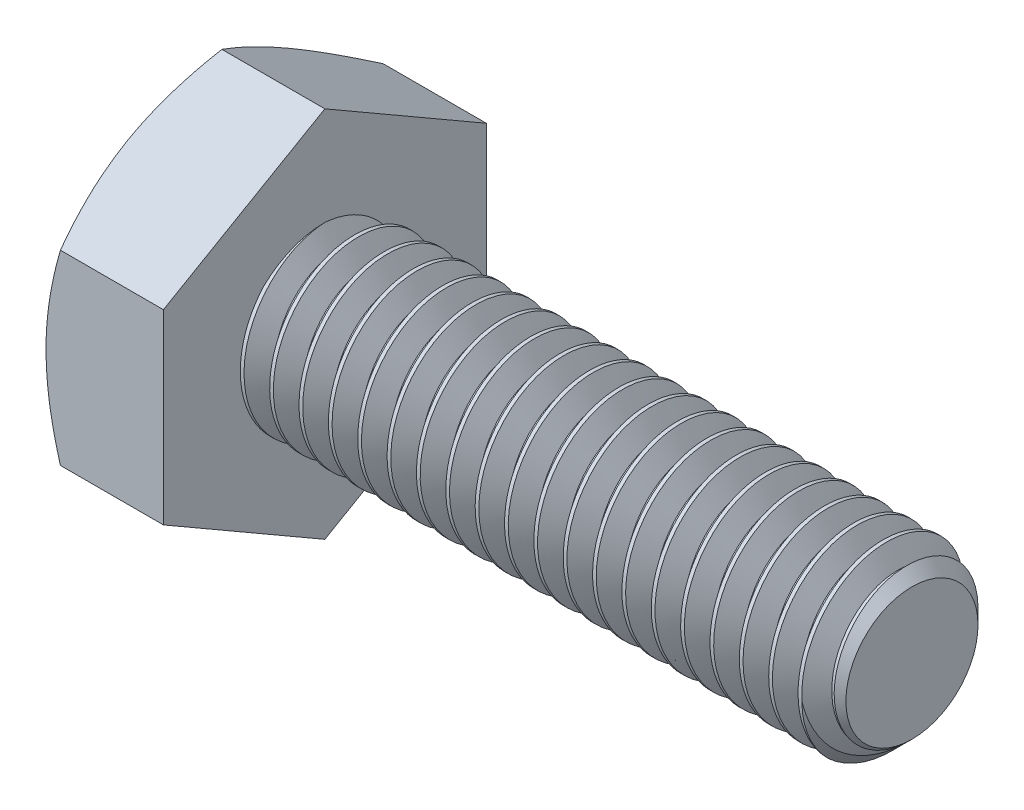
SolidWorks part; units mm, degrees
ref_plane "Front Plane" through (0, 0, 0) normal (0, 0, 1) x (1, 0, 0)
ref_plane "Top Plane" through (0, 0, 0) normal (0, 1, 0) x (1, 0, 0)
ref_plane "Right Plane" through (0, 0, 0) normal (1, 0, 0) x (0, 0, -1)
sketch "Sketch1" plane through (0, 0, 0) normal (0, 0, 1) x (1, 0, 0)
  line L0 (-6, 0) -> (6, 0) construction
  line L1 (-4, 2.75) -> (-4, -2.75) construction
  line L2 (-6, 2.75) -> (-6, -2.75) construction
  line L3 (6, 1.5) -> (6, -1.5) construction
  point P8 (4.25, -1.5)
  dimension "D1" = 1.75
  dimension "Thread Dia" = 3
  dimension "Hex" = 5.5
  dimension "Head Ht" = 2
  dimension "Length" = 10
ref_plane "Plane2" through (6, 0, 0) normal (1, 0, 0) x (0, 0, -1)
sketch "Sketch2" plane through (6, 0, 0) normal (1, 0, 0) x (0, 0, -1)
  circle A0 centre (0, 0) radius 1.5
extrude "Boss-Extrude1" add sketch "Sketch2" against normal up to vertex (10 mm away) up to point (-4, -2.75, 0)
sketch "Sketch4" plane through (6, 0, 0) normal (1, 0, 0) x (0, 0, -1)
  circle A1 centre (0, 0) radius 1.5
  circle A2 centre (0, 0) radius 1.5
  dimension "D1" = 0
curve "Helix/Spiral1" pitch 0.5 height 10.5 turns 21 parameters "Pitch"=0.5
chamfer "Chamfer1" distance 0.375 angle 45 1 edges at (6, 0, -1.5)
sketch "Sketch5" plane through (0, 0, 0) normal (0, 0, 1) x (1, 0, 0)
  line L0 (6, 1.5) -> (6.1875, 1.1752)
  line L1 (6.1875, 1.1752) -> (6.25, 1.1752)
  line L2 (6.25, 1.1752) -> (6.4375, 1.5)
  line L3 (6, 1.5) -> (6.4375, 1.5)
  line L4 (6.2187, 1.1752) -> (6.2187, 1.5) construction
  line L5 (6.0937, 1.3376) -> (6.3437, 1.3376) construction
  line L6 (6, -1.5) -> (6, 1.5) construction
  dimension "D1" = 60
  dimension "D2" = 0.0625
  dimension "D3" = 0.25
sweep "Cut-Sweep1" cut profiles "Sketch5" path "Helix/Spiral1"
sketch "Sketch3" plane through (-4, 0, 0) normal (-1, 0, 0) x (0, 0, 1)
  line L0 (0, 2.75) -> (0, -2.75) construction
  line L1 (-2.75, -1.5877) -> (0, -3.1754)
  line L2 (0, -3.1754) -> (2.75, -1.5877)
  line L3 (2.75, -1.5877) -> (2.75, 1.5877)
  line L4 (2.75, 1.5877) -> (0, 3.1754)
  line L5 (0, 3.1754) -> (-2.75, 1.5877)
  line L6 (-2.75, 1.5877) -> (-2.75, -1.5877)
  circle A0 centre (0, 0) radius 2.75 construction
extrude "Boss-Extrude2" add sketch "Sketch3" along normal up to vertex (2 mm away) up to point (-6, -2.75, 0)
sketch "Sketch6" plane through (-6, 0, 0) normal (-1, 0, 0) x (0, 0, 1)
  circle A0 centre (0, 0) radius 2.75 construction
  circle A1 centre (0, 0) radius 2.75
extrude "Cut-Extrude1" cut sketch "Sketch6" against normal through all draft 60 flip side to cut
sketch "Sketch7" plane through (-6, 0, 0) normal (-1, 0, 0) x (0, 0, 1)
  line L0 (0, 0) -> (0, 2.75) construction
  line L2 (0, 2.75) -> (0, -2.75) construction
  line L3 (-2.3816, 1.375) -> (2.3816, 1.375) construction
  circle A1 centre (0, 0) radius 2.75 construction
  text T0 "8.8\r\n" font "Arial" height in points 4
  point P8 (0, 1.375)
extrude "Cut-Extrude2" cut sketch "Sketch7" against normal blind 0.25
sketch "Sketch9" plane through (0, 0, 0) normal (0, 0, 1) x (1, 0, 0)
  line L0 (-4, 1.5) -> (-4, 0)
  line L1 (-4, 0) -> (-46.5, 0)
  line L2 (-46.5, 0) -> (-48, 1.5)
  line L3 (-48, 1.5) -> (-4, 1.5)
  line L4 (-6, 0) -> (6, 0) construction
  line L5 (-4, 2.75) -> (-4, -2.75) construction
  line L6 (6, 1.5) -> (6, -1.5) construction
  dimension "D1" = 45
  dimension "MinThreadLg" = 54
revolve "Revolve1" [suppressed] add sketch "Sketch9" angle 360 about L1
equation "\"D2@Sketch5\" = \"Pitch@Helix/Spiral1\"*.125"
equation "\"D3@Sketch5\" = \"Pitch@Helix/Spiral1\"*.50"
equation "\"D3@Helix/Spiral1\" = \"Length@Sketch1\"+\"Pitch@Helix/Spiral1\""
equation "\"D1@Chamfer1\" = \"Pitch@Helix/Spiral1\"*.750"
equation "\"D1@Sketch1\" = \"Pitch@Helix/Spiral1\"*3.50"
